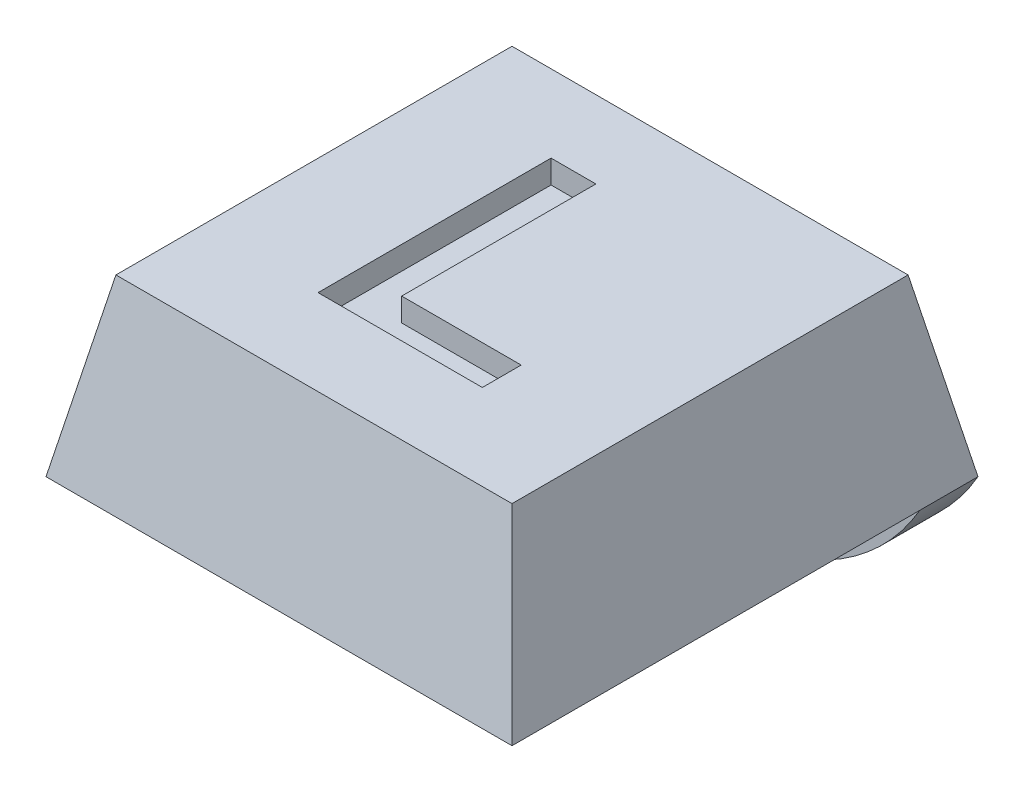
SolidWorks part; units mm, degrees
ref_plane "Front Plane" through (0, 0, 0) normal (0, 0, 1) x (1, 0, 0)
ref_plane "Top Plane" through (0, 0, 0) normal (0, 1, 0) x (1, 0, 0)
ref_plane "Right Plane" through (0, 0, 0) normal (1, 0, 0) x (0, 0, -1)
sketch "Sketch1" plane through (0, 0, 0) normal (0, 1, 0) x (1, 0, 0)
  line L1 (0, 0) -> (8, 0)
  line L2 (0, 0) -> (0, 8)
  line L3 (0, 8) -> (8, 8)
  line L4 (8, 0) -> (8, 8)
  dimension "D1" = 8
  dimension "D2" = 8
extrude "Boss-Extrude1" add sketch "Sketch1" along normal blind 3
sketch "Sketch2" plane through (0, 0, 0) normal (0, 0, 1) x (1, 0, 0)
  line L0 (0, 0) -> (0.6, 3)
  line L1 (0, 3) -> (8, 3) construction
  line L2 (0.6, 3) -> (0, 3)
  line L3 (0, 3) -> (0, 0)
  line L4 (8, 0) -> (7.4, 3)
  line L5 (7.4, 3) -> (8, 3)
  line L6 (8, 3) -> (8, 0)
  dimension "D1" = 0.6
  dimension "D2" = 0.6
extrude "Cut-Extrude1" cut sketch "Sketch2" against normal through all both and the other way through all
sketch "Sketch3" plane through (0, 0, 0) normal (1, 0, 0) x (0, 0, -1)
  line L0 (0, 0) -> (0.6, 3)
  line L1 (8, 3) -> (0, 3) construction
  line L2 (0.6, 3) -> (0, 3)
  line L3 (0, 3) -> (0, 0)
  line L4 (8, 3) -> (7.4, 3)
  line L5 (7.4, 3) -> (8, 0)
  line L6 (8, 3) -> (8, 0)
  dimension "D1" = 0.6
  dimension "D2" = 0.6
extrude "Cut-Extrude2" cut sketch "Sketch3" along normal blind 11
sketch "Sketch4" plane through (0, 0, 0) normal (0, -1, 0) x (1, 0, 0)
  line L0 (8, 0) -> (8, -8) construction
  line L3 (0, 0) -> (8, 0) construction
  circle A0 centre (4, -3.75) radius 1.75
  dimension "D1" = 3.5
  dimension "D2" = 4
  dimension "D3" = 3.75
extrude "Cut-Extrude3" cut sketch "Sketch4" against normal blind 0.4
sketch "Sketch5" plane through (0, 0, 0) normal (0, -1, 0) x (1, 0, 0)
  line L0 (8, 0) -> (8, -8) construction
  line L1 (0, -8) -> (8, -8)
  line L2 (0, -8) -> (0, -7)
  line L3 (0, -7) -> (8, -7)
  line L4 (8, -8) -> (8, -7)
  dimension "D1" = 1
extrude "Boss-Extrude2" add sketch "Sketch5" along normal blind 2
fillet "Fillet1" radius 4 2 edges at (8, -2, -7.5) (0, -2, -7.5)
sketch "Sketch6" plane through (0, 3, 0) normal (0, 1, 0) x (1, 0, 0)
  text T0 "L" font "Arial" height 4
extrude "Cut-Extrude4" cut sketch "Sketch6" against normal blind 0.4
